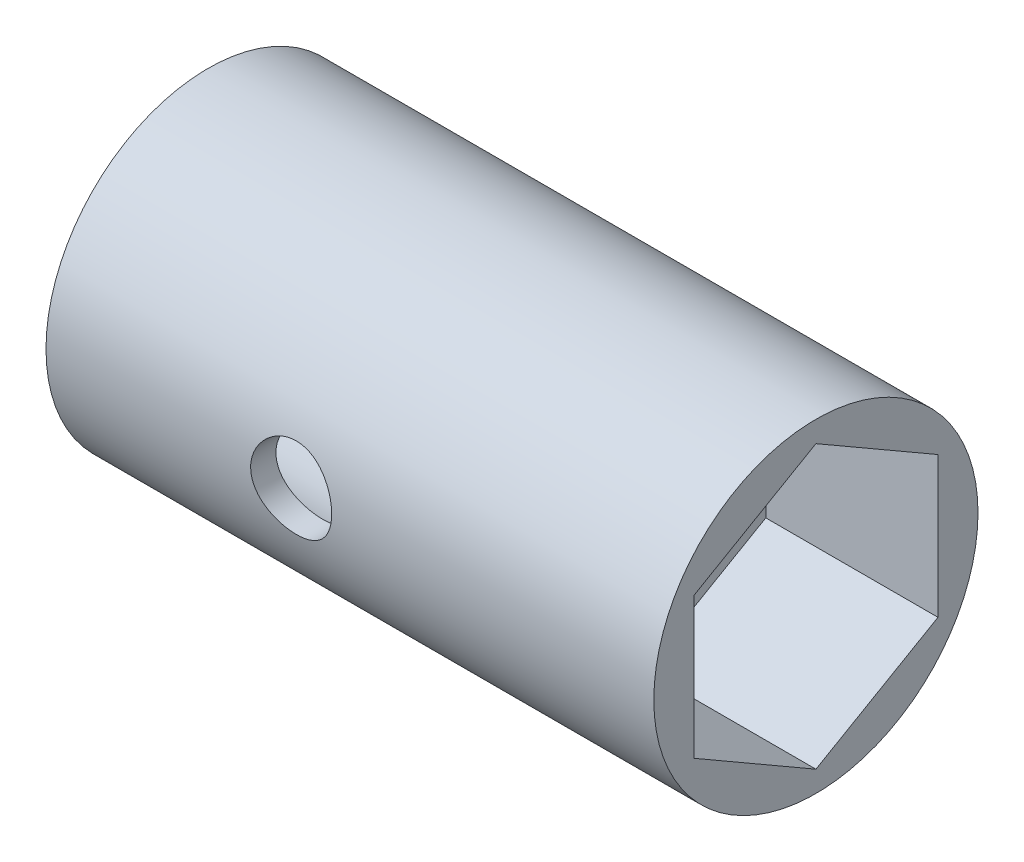
SolidWorks part; units mm, degrees
ref_plane "Alzado" through (0, 0, 0) normal (0, 0, 1) x (1, 0, 0)
ref_plane "Planta" through (0, 0, 0) normal (0, 1, 0) x (1, 0, 0)
ref_plane "Vista lateral" through (0, 0, 0) normal (1, 0, 0) x (0, 0, -1)
sketch "Croquis1" plane through (0, 0, 0) normal (1, 0, 0) x (0, 0, -1)
  line L1 (0, -6.9282) -> (6, -3.4641) construction
  line L2 (6, -3.4641) -> (6, 3.4641) construction
  line L3 (6, 3.4641) -> (0, 6.9282) construction
  line L4 (0, 6.9282) -> (-6, 3.4641) construction
  line L5 (-6, 3.4641) -> (-6, -3.4641) construction
  line L6 (-6, -3.4641) -> (0, -6.9282) construction
  circle A0 centre (0, 0) radius 6.4 construction
  circle A1 centre (0, 0) radius 6 construction
  circle A2 centre (0, 0) radius 8
  point P11 (0, 0)
  dimension "D2" = 12.8
  dimension "D3" = 16
  dimension "D1" = 12
extrude "Saliente-Extruir1" add sketch "Croquis1" along normal blind 20
sketch "Croquis2" plane through (20, 0, 0) normal (1, 0, 0) x (0, 0, -1)
  line L1 (0, -6.9571) -> (6.025, -3.4785)
  line L2 (6.025, -3.4785) -> (6.025, 3.4785)
  line L3 (6.025, 3.4785) -> (0, 6.9571)
  line L4 (0, 6.9571) -> (-6.025, 3.4785)
  line L5 (-6.025, 3.4785) -> (-6.025, -3.4785)
  line L6 (-6.025, -3.4785) -> (0, -6.9571)
  circle A0 centre (0, 0) radius 6.025 construction
  dimension "D1" = 12.05
extrude "Cortar-Extruir1" cut sketch "Croquis2" against normal blind 8.5
sketch "Croquis3" plane through (0, 0, 0) normal (-1, 0, 0) x (0, 0, 1)
  circle A0 centre (0, 0) radius 6.75
  dimension "D1" = 13.5
extrude "Cortar-Extruir2" cut sketch "Croquis3" against normal blind 9
sketch "Croquis4" plane through (9, 0, 0) normal (-1, 0, 0) x (0, 0, 1)
  circle A0 centre (0, 0) radius 2.025
  dimension "D1" = 4.05
extrude "Cortar-Extruir3" cut sketch "Croquis4" against normal up to next
sketch "Croquis5" plane through (0, 0, 0) normal (0, 0, 1) x (1, 0, 0)
  circle A0 centre (2.1, 0) radius 2
  dimension "D1" = 4
  dimension "D2" = 2.1
extrude "Cortar-Extruir4" cut sketch "Croquis5" against normal through all and the other way blind 9
sketch "Croquis6" plane through (0, 0, 0) normal (-1, 0, 0) x (0, 0, 1)
  circle A0 centre (0, 0) radius 6.75 construction
  circle A1 centre (0, 0) radius 8
  circle A2 centre (0, 0) radius 8
  circle A3 centre (0, 0) radius 6.75
  dimension "D1" = 0
extrude "Saliente-Extruir2" add sketch "Croquis6" along normal blind 10
equation "\"D1@Croquis2\"=12+0.05"
equation "\"D1@Croquis3\"=12.8+0.7"
